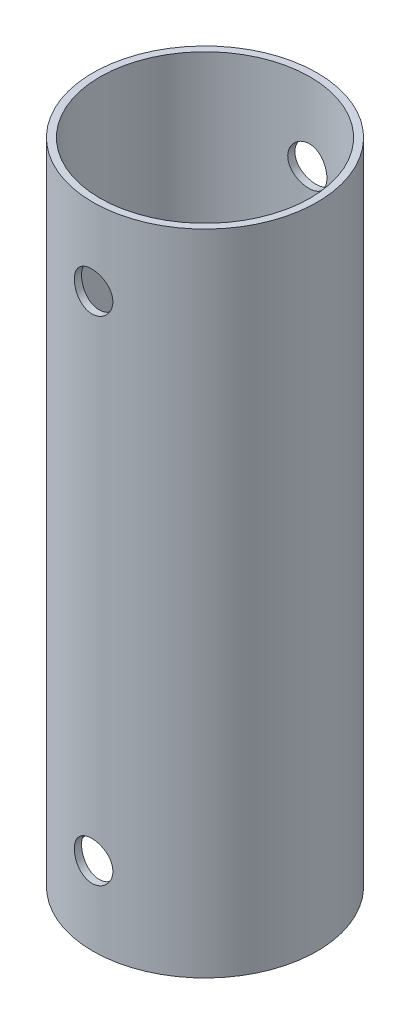
SolidWorks part; units mm, degrees
material "PETG"
ref_plane "Front Plane" through (0, 0, 0) normal (0, 0, 1) x (1, 0, 0)
ref_plane "Top Plane" through (0, 0, 0) normal (0, 1, 0) x (1, 0, 0)
ref_plane "Right Plane" through (0, 0, 0) normal (1, 0, 0) x (0, 0, -1)
sketch "Sketch1" plane through (0, 0, 0) normal (0, 1, 0) x (1, 0, 0)
  circle A0 centre (0, 0) radius 15.875
  circle A1 centre (0, 0) radius 14.875
extrude "Boss-Extrude1" add sketch "Sketch1" along normal blind 91.814
sketch "Sketch2" plane through (0, 0, 0) normal (0, 0, 1) x (1, 0, 0)
  line L0 (-41.6535, 80.814) -> (41.3866, 80.814) construction
  line L1 (-41.6535, 11) -> (41.3866, 11) construction
  line L4 (0, 162.6204) -> (0, -4.7636) construction
  line L5 (0, 0) -> (-46.9074, 0) construction
  line L6 (-15.875, 91.814) -> (47.514, 91.814) construction
  circle A0 centre (-0.1335, 80.814) radius 2.75
  circle A1 centre (-0.1335, 11) radius 2.75
  dimension "D1" = 11
  dimension "D2" = 11
extrude "Cut-Extrude1" cut sketch "Sketch2" against normal blind 154.2 and the other way blind 154.2
